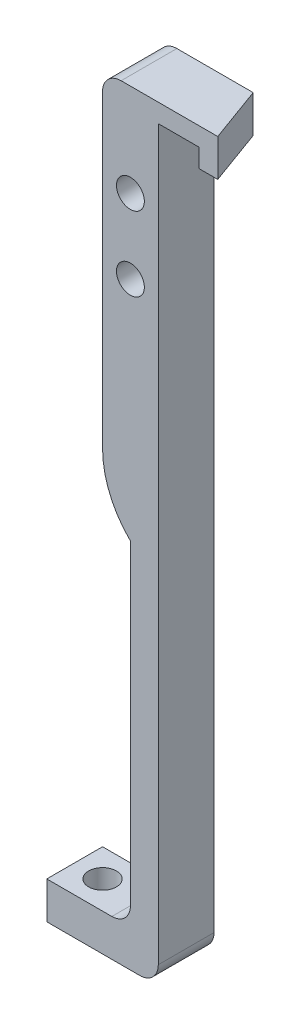
SolidWorks part; units mm, degrees
ref_plane "Front Plane" through (0, 0, 0) normal (0, 0, 1) x (1, 0, 0)
ref_plane "Top Plane" through (0, 0, 0) normal (0, 1, 0) x (1, 0, 0)
ref_plane "Right Plane" through (0, 0, 0) normal (1, 0, 0) x (0, 0, -1)
sketch "Sketch1" plane through (0, 0, 0) normal (1, 0, 0) x (0, 0, -1)
  line L1 (0, 0) -> (7.62, 0)
  line L2 (0, 0) -> (0, 104.648)
  line L3 (0, 104.648) -> (7.62, 104.648)
  line L4 (7.62, 0) -> (7.62, 104.648)
  dimension "D1" = 7.62
  dimension "D2" = 104.648
extrude "Boss-Extrude1" add sketch "Sketch1" along normal blind 7.62
sketch "Sketch2" plane through (0, 0, 0) normal (-1, 0, 0) x (0, 0, 1)
  line L0 (-7.62, 0) -> (-7.62, 104.648) construction
  line L1 (0, 0) -> (-7.62, 0)
  line L2 (0, 0) -> (0, 5.08)
  line L3 (0, 5.08) -> (-7.62, 5.08)
  line L4 (-7.62, 0) -> (-7.62, 5.08)
  dimension "D1" = 5.08
extrude "Boss-Extrude2" add sketch "Sketch2" along normal blind 7.62
sketch "Sketch4" plane through (7.62, 0, 0) normal (1, 0, 0) x (0, 0, -1)
  line L0 (7.62, 0) -> (7.62, 104.648) construction
  line L1 (0, 104.648) -> (7.62, 104.648)
  line L2 (0, 104.648) -> (0, 102.108)
  line L3 (0, 102.108) -> (7.62, 102.108)
  line L4 (7.62, 104.648) -> (7.62, 102.108)
  dimension "D1" = 2.54
extrude "Boss-Extrude3" add sketch "Sketch4" along normal blind 8.128
sketch "Sketch5" plane through (0, 102.108, 0) normal (0, -1, 0) x (1, 0, 0)
  line L1 (15.748, 0) -> (12.9745, -7.62)
  line L2 (15.748, -7.62) -> (7.62, -7.62) construction
  line L3 (15.748, 0) -> (15.748, -7.62) construction
  line L4 (10.4345, -7.62) -> (13.208, 0)
  line L5 (15.748, 0) -> (7.62, 0) construction
  line L6 (15.748, 0) -> (13.208, 0)
  line L7 (10.4345, -7.62) -> (12.9745, -7.62)
  dimension "D1" = 20
  dimension "D2" = 2.54
  dimension "D3" = 20
extrude "Boss-Extrude4" add sketch "Sketch5" along normal blind 2.54
hole_wizard "#6 Clearance Hole1" positions "Sketch7" profile "Sketch6" hole size "#6" standard "ANSI Inch" end condition up to next
sketch "Sketch7" plane through (0, 5.08, 0) normal (0, 1, 0) x (1, 0, 0)
  line L2 (0, 0) -> (0, 7.62) construction
  line L3 (-7.62, 7.62) -> (0, 7.62) construction
  point P0 (-3.81, 3.81)
  dimension "D1" = 3.81
  dimension "D2" = 3.81
sketch "Sketch6" plane through (-3.81, 5.08, -3.81) normal (1, 0, 0) x (0, 0, 1)
  line L0 (0, 0) -> (0, 5.08)
  line L1 (0, 5.08) -> (1.8986, 5.08)
  line L2 (1.8986, 5.08) -> (1.8986, 0)
  line L5 (1.8986, 0) -> (0, 0)
  line L11 (0, -6.35) -> (0, 107.95) construction
  dimension "Thru Hole Dia." = 3.7973
  dimension "Thru Hole Depth" = 5.08
sketch "Sketch8" plane through (0, 102.108, 0) normal (0, -1, 0) x (1, 0, 0)
  line L0 (15.748, -7.62) -> (12.9745, -7.62)
  line L1 (12.9745, -7.62) -> (15.748, 0)
  line L2 (15.748, 0) -> (15.748, -7.62)
extrude "Cut-Extrude1" cut sketch "Sketch8" against normal blind 2.54
ref_plane "Plane1" through (0, 0, -10.16) normal (0, 0, -1) x (-1, 0, 0)
sketch "Sketch12" plane through (0, 0, 0) normal (-1, 0, 0) x (0, 0, 1)
  line L0 (0, 104.648) -> (0, 5.08) construction
  line L1 (-7.62, 5.08) -> (0, 5.08)
  line L2 (-7.62, 5.08) -> (-7.62, 50.8)
  line L3 (-7.62, 50.8) -> (0, 50.8)
  line L4 (0, 5.08) -> (0, 50.8)
  dimension "D1" = 45.72
extrude "Cut-Extrude2" cut sketch "Sketch12" against normal blind 3.81
fillet "Fillet2" radius 12.7 1 edges at (0, 50.8, -3.81)
fillet "Fillet3" radius 2.54 3 edges at (3.81, 5.08, -3.81) (7.62, 0, -3.81) (0, 104.648, -3.81)
sketch "Sketch14" plane through (0, 0, 0) normal (0, 0, 1) x (1, 0, 0)
  line L0 (0, 102.108) -> (0, 59.8696) construction
  line L1 (15.748, 104.648) -> (2.54, 104.648) construction
  circle A0 centre (3.81, 91.948) radius 1.905
  circle A1 centre (3.81, 81.788) radius 1.905
  dimension "D5" = 3.81
  dimension "D6" = 3.81
  dimension "D1" = 3.81
  dimension "D2" = 3.81
  dimension "D3" = 12.7
  dimension "D4" = 10.16
extrude "Cut-Extrude4" cut sketch "Sketch14" against normal through all
